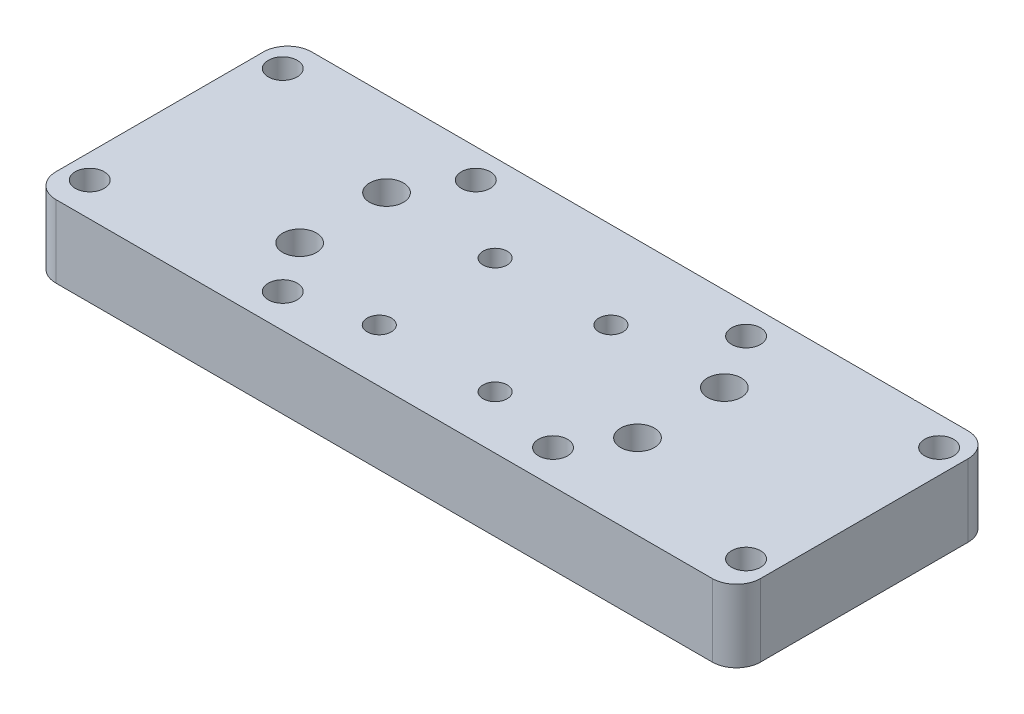
SolidWorks part; units mm, degrees
ref_plane "Front Plane" through (0, 0, 0) normal (0, 0, 1) x (1, 0, 0)
ref_plane "Top Plane" through (0, 0, 0) normal (0, 1, 0) x (1, 0, 0)
ref_plane "Right Plane" through (0, 0, 0) normal (1, 0, 0) x (0, 0, -1)
sketch "Sketch1" plane through (0, 0, 0) normal (0, 1, 0) x (1, 0, 0)
  line L0 (0, 0) -> (5, 0)
  line L1 (0, 0) -> (130, 0)
  line L2 (0, 0) -> (0, 63)
  line L3 (0, 63) -> (130, 63)
  line L4 (130, 0) -> (130, 63)
  line L5 (0, 0) -> (0, -37)
  line L6 (0, -37) -> (130, -37)
  line L7 (130, -37) -> (130, 0)
  line L9 (0, -37) -> (130, -37)
  line L10 (0, -37) -> (0, -27)
  line L11 (0, -27) -> (130, -27)
  line L12 (130, -37) -> (130, -27)
  circle A0 centre (5, 57) radius 3
  circle A1 centre (45, 57) radius 3
  circle A2 centre (5, 17) radius 3
  circle A3 centre (45, 17) radius 3
  circle A4 centre (85, 57) radius 3
  circle A5 centre (125, 57) radius 3
  circle A6 centre (85, 17) radius 3
  circle A7 centre (125, 17) radius 3
  dimension "D1" = 10
extrude "Boss-Extrude1" add sketch "Sketch1" along normal blind 10 contours L1 L4 L3 L2 L0 A7 A6 A5 A4 A3 A2 A1 A0 | L5 L11 L7 L1 L0 | L11 L5 L6 L7 region at (65, 0, -31.3438) region at (65, 0, 13.5) region at (65, 0, 32)
sketch "Sketch2" plane through (0, 10, 0) normal (0, 1, 0) x (1, 0, 0)
  line L0 (130, -37) -> (130, 63) construction
  line L1 (0, -37) -> (130, -37)
  line L2 (0, -37) -> (0, -28.977)
  line L3 (0, -28.977) -> (130, -28.977)
  line L4 (130, -37) -> (130, -28.977)
extrude "Boss-Extrude2" add sketch "Sketch2" along normal blind 75
fillet "Fillet1" radius 0.1 4 edges at (0, 85, 32.9885) (130, 85, 32.9885) (130, 5, -63) (0, 5, -63)
sketch "Sketch3" plane through (0, 85, 0) normal (0, 1, 0) x (1, 0, 0)
  line L0 (130, -28.977) -> (129.9, -28.977) construction
  line L1 (0, -37) -> (130, -37)
  line L2 (0, -37) -> (0, -28.977)
  line L3 (0, -28.977) -> (130, -28.977)
  line L4 (130, -37) -> (130, -28.977)
  line L5 (130, -28.977) -> (130, -37) construction
extrude "Cut-Extrude1" cut sketch "Sketch3" against normal blind 75
sketch "Sketch4" plane through (0, 0, 37) normal (0, 0, 1) x (1, 0, 0)
  line L1 (0, 0) -> (130, 0)
  line L2 (0, 0) -> (0, 10)
  line L3 (0, 10) -> (130, 10)
  line L4 (130, 0) -> (130, 10)
extrude "Cut-Extrude2" cut sketch "Sketch4" against normal blind 37
sketch "Sketch5" plane through (0, 10, 0) normal (0, 1, 0) x (1, 0, 0)
  line L0 (130, 0) -> (130, 62.9) construction
  line L1 (0, 0) -> (130, 0)
  line L2 (0, 0) -> (0, 10)
  line L3 (0, 10) -> (130, 10)
  line L4 (130, 0) -> (130, 10)
  dimension "D1" = 10
extrude "Boss-Extrude4" add sketch "Sketch5" along normal blind 75
fillet "Fillet2" radius 5 2 edges at (130, 85, -5) (0, 85, -5)
sketch "Sketch6" plane through (0, 0, -10) normal (0, 0, -1) x (-1, 0, 0)
  circle A0 centre (-113, 47.5) radius 10
  circle A1 centre (-65, 47.5) radius 7.5
  circle A2 centre (-17, 47.5) radius 10
  circle A3 centre (-113, 71.5) radius 3.5
  circle A4 centre (-65, 74.04) radius 3.5
  circle A5 centre (-17, 71.5) radius 3.5
  circle A6 centre (-17, 23.5) radius 3.5
  circle A7 centre (-65, 21) radius 3.5
  circle A8 centre (-113, 23.5) radius 3.5
  circle A9 centre (-88.58, 71.06) radius 2.5
  circle A10 centre (-41.44, 71.06) radius 2.5
  circle A11 centre (-41.44, 23.92) radius 2.5
  circle A12 centre (-88.58, 23.92) radius 2.5
extrude "Cut-Extrude3" cut sketch "Sketch6" against normal blind 10
sketch "Sketch7" plane through (0, 0, -10) normal (0, 0, -1) x (-1, 0, 0)
  circle A0 centre (-65, 47.5) radius 19.1
extrude "Cut-Extrude4" cut sketch "Sketch7" against normal blind 10
sketch "Sketch8" plane through (0, 0, -10) normal (0, 0, -1) x (-1, 0, 0)
  circle A0 centre (-65, 74.04) radius 3.5
  circle A1 centre (-65, 21) radius 3.5
extrude "Boss-Extrude5" add sketch "Sketch8" against normal blind 10
sketch "Sketch9" plane through (0, 85, 0) normal (0, 1, 0) x (1, 0, 0)
  line L1 (0, 10) -> (130, 10)
  line L2 (0, 10) -> (0, 0)
  line L3 (0, 0) -> (130, 0)
  line L4 (130, 10) -> (130, 0)
extrude "Cut-Extrude5" cut sketch "Sketch9" against normal through all
fillet "Fillet3" radius 5 rebuild error yes
sketch "Sketch10" plane through (130, 0, 0) normal (1, 0, 0) x (0, 0, -1)
  line L1 (10, 10) -> (63, 10)
  line L2 (10, 10) -> (10, 0)
  line L3 (10, 0) -> (63, 0)
  line L4 (63, 10) -> (63, 0)
extrude "Boss-Extrude6" add sketch "Sketch10" along normal blind 30
sketch "Sketch11" plane through (0, 10, 0) normal (0, 1, 0) x (1, 0, 0)
  line L0 (45, 57) -> (101, 57)
  line L1 (101, 57) -> (101, 17)
  line L2 (101, 17) -> (141, 17)
  line L3 (141, 17) -> (141, 57)
  circle A0 centre (101, 57) radius 3
  circle A1 centre (141, 57) radius 3
  circle A2 centre (101, 17) radius 3
  circle A3 centre (141, 17) radius 3
extrude "Cut-Extrude6" cut sketch "Sketch11" against normal blind 30 contours L1 A0 L0 | L0 A0 L1 | L1 A2 L2 | L2 A2 L1 | L3 A3 L2 | L2 A3 L3 | A1 region at (101.4244, 10, -57.4244) region at (138.9387, 10, -59.0613) region at (139.7268, 10, -18.2732) region at (141.4244, 10, -16.5756) region at (102.2732, 10, -18.2732) region at (100.5756, 10, -16.5756) region at (99.7268, 10, -55.7268)
sketch "Sketch12" plane through (0, 10, 0) normal (0, 1, 0) x (1, 0, 0)
  circle A0 centre (85, 57) radius 3
  circle A1 centre (125, 57) radius 3
  circle A2 centre (85, 17) radius 3
  circle A3 centre (125, 17) radius 3
extrude "Boss-Extrude7" add sketch "Sketch12" against normal blind 10
sketch "Sketch14" plane through (160, 0, 0) normal (1, 0, 0) x (0, 0, -1)
  line L1 (10, 10) -> (63, 10)
  line L2 (10, 10) -> (10, 0)
  line L3 (10, 0) -> (63, 0)
  line L4 (63, 10) -> (63, 0)
extrude "Cut-Extrude7" cut sketch "Sketch14" against normal blind 14
sketch "Sketch15" plane through (0, 0, 0) normal (-1, 0, 0) x (0, 0, 1)
  line L1 (-10, 10) -> (-63, 10)
  line L2 (-10, 10) -> (-10, 0)
  line L3 (-10, 0) -> (-63, 0)
  line L4 (-63, 10) -> (-63, 0)
extrude "Cut-Extrude9" cut sketch "Sketch15" along direction (-1, 0, 0) on the side against the normal blind 1.5
sketch "Sketch16" plane through (1.5, 0, 0) normal (-1, 0, 0) x (0, 0, 1)
  line L1 (-63, 10) -> (-10, 10)
  line L2 (-63, 10) -> (-63, 0)
  line L3 (-63, 0) -> (-10, 0)
  line L4 (-10, 10) -> (-10, 0)
extrude "Boss-Extrude8" add sketch "Sketch16" along normal blind 1.5
fillet "Fillet5" radius 5 4 edges at (146, 5, -63) (146, 5, -10) (0, 5, -10) (0, 5, -63)
sketch "Sketch17" plane through (0, 10, 0) normal (0, 1, 0) x (1, 0, 0)
  circle A0 centre (61, 48.5) radius 2.5
  circle A1 centre (85, 48.5) radius 2.5
  circle A2 centre (61, 24.5) radius 2.5
  circle A3 centre (85, 24.5) radius 2.5
extrude "Cut-Extrude11" cut sketch "Sketch17" against normal blind 10
sketch "Sketch18" plane through (0, 10, 0) normal (0, 1, 0) x (1, 0, 0)
  line L0 (61, 24.5) -> (61, 21)
  line L1 (85, 21) -> (85, 18.8978)
  line L2 (61, 48.5) -> (61, 45)
  line L3 (85, 48.5) -> (85, 45)
  circle A0 centre (61, 45) radius 2.5
  circle A1 centre (85, 45) radius 2.5
  circle A2 centre (61, 21) radius 2.5
  circle A3 centre (85, 21) radius 2.5
  circle M2 centre (61, 24.5) radius 2.5
  circle M3 centre (85, 48.5) radius 2.5
  circle M4 centre (61, 48.5) radius 2.5
extrude "Cut-Extrude12" cut sketch "Sketch18" against normal blind 10 contours A2 M2 | A0 M4 | A1 M3 | A3 region at (61, 10, -20.5945) region at (61, 10, -44.5945) region at (85, 10, -44.5945) region at (84.0797, 10, -18.7463)
sketch "Sketch19" plane through (0, 10, 0) normal (0, 1, 0) x (1, 0, 0)
  circle A0 centre (61, 48.5) radius 2.5
  circle A1 centre (61, 45) radius 2.5
  circle A2 centre (85, 48.5) radius 2.5
  circle A3 centre (85, 45) radius 2.5
  circle A4 centre (85, 24.5) radius 2.5
  circle A5 centre (61, 21) radius 2.5
  circle A6 centre (61, 24.5) radius 2.5
  circle A7 centre (85, 21) radius 2.5
  arc M2 (83.2146, 22.75) -> (86.7854, 22.75) centre (85, 24.5) cw
  arc M4 (83.2146, 46.75) -> (86.7854, 46.75) centre (85, 48.5) cw
  arc M6 (59.2146, 46.75) -> (62.7854, 46.75) centre (61, 48.5) cw
  arc M8 (59.2146, 22.75) -> (62.7854, 22.75) centre (61, 24.5) cw
extrude "Boss-Extrude9" add sketch "Sketch19" against normal blind 10 contours A1 M6 | A3 M4 | A7 M2 | A5 M8 region at (61, 10, -48.9055) region at (85, 10, -48.9055) region at (85, 10, -24.9055) region at (61, 10, -24.9055)
sketch "Sketch20" plane through (0, 10, 0) normal (0, 1, 0) x (1, 0, 0)
  circle A0 centre (38, 45.5) radius 3.5
  circle A1 centre (38, 27.5) radius 3.5
  circle A2 centre (108, 45.5) radius 3.5
  circle A3 centre (108, 27.5) radius 3.5
extrude "Cut-Extrude13" cut sketch "Sketch20" against normal through all
sketch "Sketch21" plane through (0, 10, 0) normal (0, 1, 0) x (1, 0, 0)
  line L0 (5, 63) -> (141, 63)
  line L1 (146, 58) -> (146, 15)
  line L2 (141, 10) -> (5, 10)
  line L3 (0, 58) -> (0, 15)
  circle A0 centre (45, 57) radius 3
  circle A1 centre (5, 57) radius 3
  circle A2 centre (5, 17) radius 3
  circle A3 centre (38, 45.5) radius 3.5
  circle A4 centre (38, 27.5) radius 3.5
  circle A5 centre (45, 17) radius 3
  circle A6 centre (61, 21) radius 2.5
  circle A7 centre (61, 45) radius 2.5
  circle A8 centre (85, 45) radius 2.5
  circle A9 centre (85, 21) radius 2.5
  circle A10 centre (101, 17) radius 3
  circle A11 centre (108, 27.5) radius 3.5
  circle A12 centre (108, 45.5) radius 3.5
  circle A13 centre (101, 57) radius 3
  circle A14 centre (141, 57) radius 3
  circle A15 centre (141, 17) radius 3
  circle A16 centre (141, 58) radius 5
  circle A17 centre (141, 15) radius 5
  circle A18 centre (5, 15) radius 5
  circle A19 centre (5, 58) radius 5
  circle M1 centre (108, 27.5) radius 3.5
  circle M2 centre (108, 45.5) radius 3.5
  circle M3 centre (38, 27.5) radius 3.5
  circle M4 centre (38, 45.5) radius 3.5
  circle M5 centre (85, 21) radius 2.5
  circle M6 centre (85, 45) radius 2.5
  circle M7 centre (61, 45) radius 2.5
  circle M8 centre (61, 21) radius 2.5
  line M9 (146, 15) -> (146, 58)
  arc M10 (146, 58) -> (141, 63) centre (141, 58) ccw
  line M11 (141, 63) -> (130, 63)
  line M12 (130, 63) -> (130, 62.9)
  arc M13 (130, 62.9) -> (129.9, 63) centre (129.9, 62.9) ccw
  line M14 (129.9, 63) -> (5, 63)
  arc M15 (5, 63) -> (0, 58) centre (5, 58) ccw
  line M16 (0, 58) -> (0, 15)
  arc M17 (0, 15) -> (5, 10) centre (5, 15) ccw
  line M18 (5, 10) -> (141, 10)
  arc M19 (141, 10) -> (146, 15) centre (141, 15) ccw
  circle M20 centre (5, 57) radius 3
  circle M21 centre (45, 57) radius 3
  circle M22 centre (5, 17) radius 3
  circle M23 centre (45, 17) radius 3
  circle M24 centre (101, 57) radius 3
  circle M25 centre (101, 17) radius 3
  circle M26 centre (141, 17) radius 3
  circle M27 centre (141, 57) radius 3
extrude "Boss-Extrude10" add sketch "Sketch21" along normal blind 5 contours A19 A18 A17 A16 M16 M18 M9 M11 M12 M13 M14 M2 M4 M6 M8 M24 M25 M23 M21 M7 M5 M3 M1 | A19 M15 M20 | A16 M10 M27 | A17 M19 M26 | A18 M17 M22 region at (73, 10, -36.5309) region at (8.4355, 10, -61.4355) region at (5, 10, -13.875) region at (144.4355, 10, -61.4355) region at (141, 10, -13.875)
